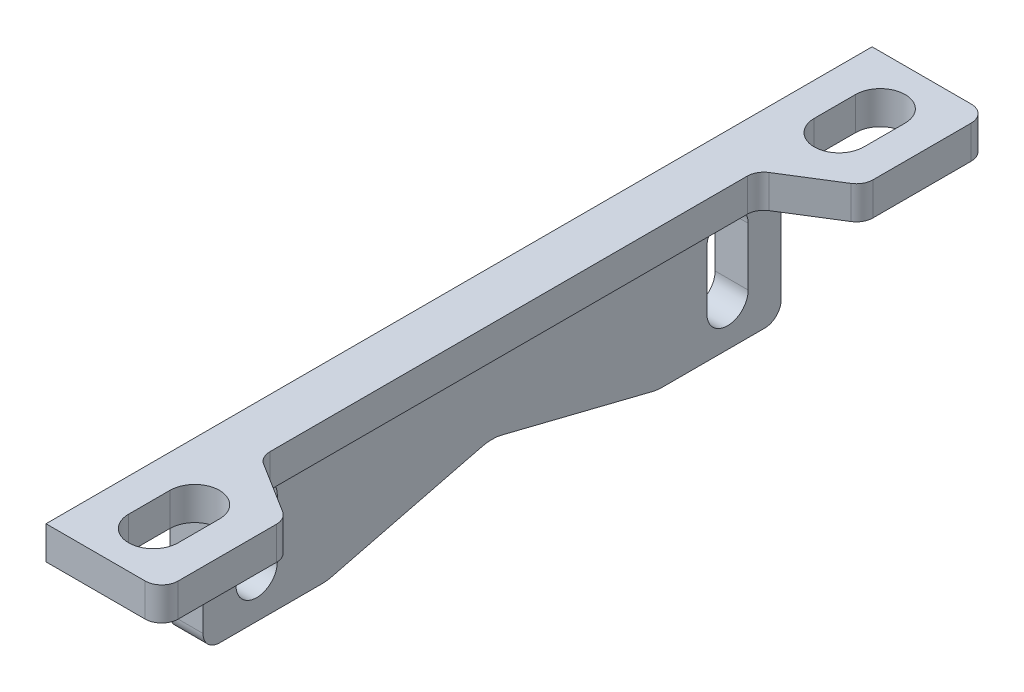
SolidWorks part; units mm, degrees
ref_plane "Front Plane" through (0, 0, 0) normal (0, 0, 1) x (1, 0, 0)
ref_plane "Top Plane" through (0, 0, 0) normal (0, 1, 0) x (1, 0, 0)
ref_plane "Right Plane" through (0, 0, 0) normal (1, 0, 0) x (0, 0, -1)
sketch "Sketch1" plane through (0, 0, 0) normal (0, 1, 0) x (1, 0, 0)
  line L2 (0, 0) -> (0, 63.5)
  line L4 (7.62, 0) -> (7.62, 63.5) construction
  line L9 (8.89, 13.97) -> (8.89, 7.62) construction
  line L10 (12.7, 13.97) -> (12.7, 7.62)
  line L11 (5.08, 13.97) -> (5.08, 7.62)
  line L12 (17.78, 0) -> (17.78, 19.05)
  line L13 (17.78, 19.05) -> (7.62, 25.4)
  line L15 (0, 0) -> (17.78, 0)
  line L16 (0, 63.5) -> (7.62, 63.5)
  line L17 (7.62, 63.5) -> (7.62, 25.4)
  arc A0 (12.7, 13.97) -> (5.08, 13.97) centre (8.89, 13.97) ccw
  arc A1 (5.08, 7.62) -> (12.7, 7.62) centre (8.89, 7.62) ccw
  point P7 (8.89, 10.795)
  dimension "D9" = 6.35
  dimension "D1" = 63.5
  dimension "D2" = 7.62
  dimension "D4" = 25.4
  dimension "D5" = 17.78
  dimension "D6" = 19.05
  dimension "D8" = 7.62
  dimension "D10" = 7.62
  dimension "D11" = 8.89
extrude "top" add sketch "Sketch1" along normal blind 5.08
sketch "Sketch2" plane through (0, 0, 0) normal (0, -1, 0) x (1, 0, 0)
  line L1 (0, -19.05) -> (5.08, -19.05)
  line L2 (0, -19.05) -> (0, -63.5)
  line L3 (0, -63.5) -> (5.08, -63.5)
  line L4 (5.08, -19.05) -> (5.08, -63.5)
  line L5 (7.62, -63.5) -> (0, -63.5) construction
  line L6 (0, -63.5) -> (0, 0) construction
  dimension "D1" = 5.08
  dimension "D2" = 19.05
extrude "bolt_attach" add sketch "Sketch2" along normal blind 19.05
sketch "Sketch3" plane through (5.08, 0, 0) normal (1, 0, 0) x (0, 0, -1)
  line L0 (27.305, -3.81) -> (27.305, -12.7) construction
  line L1 (30.48, -3.81) -> (30.48, -12.7)
  line L2 (24.13, -3.81) -> (24.13, -12.7)
  line L3 (25.4, 0) -> (63.5, 0) construction
  line L5 (63.5, -19.05) -> (63.5, 0) construction
  line L6 (63.5, -19.05) -> (63.5, -12.7)
  line L7 (63.5, -12.7) -> (38.1, -19.05)
  line L8 (63.5, -19.05) -> (19.05, -19.05) construction
  line L9 (38.1, -19.05) -> (63.5, -19.05)
  arc A0 (30.48, -3.81) -> (24.13, -3.81) centre (27.305, -3.81) ccw
  arc A1 (24.13, -12.7) -> (30.48, -12.7) centre (27.305, -12.7) ccw
  point P2 (27.305, -8.255)
  dimension "D1" = 6.35
  dimension "D2" = 3.81
  dimension "D3" = 36.195
  dimension "D4" = 8.89
  dimension "D5" = 6.35
  dimension "D6" = 25.4
extrude "boltholes_lower" cut sketch "Sketch3" against normal up to surface (5.08 mm away) up to face at (0, -4.6567, -27.5167)
fillet "mirroredfillet" radius 2.54 4 edges at (17.78, 2.54, 0) (17.78, 2.54, -19.05) (7.62, 2.54, -25.4) (2.54, -19.05, -19.05)
mirror "Mirror2" about plane through (0, 5.08, -63.5) normal (0, 0, 1) of bodies 105 102
fillet "centerfillet" radius 6.35 3 edges at (2.54, -19.05, -88.9) (2.54, -19.05, -38.1) (2.54, -12.7, -63.5)
chamfer "Chamfer1" distance 2.54 angle 45 1 edges at (5.08, 0, -63.5)
